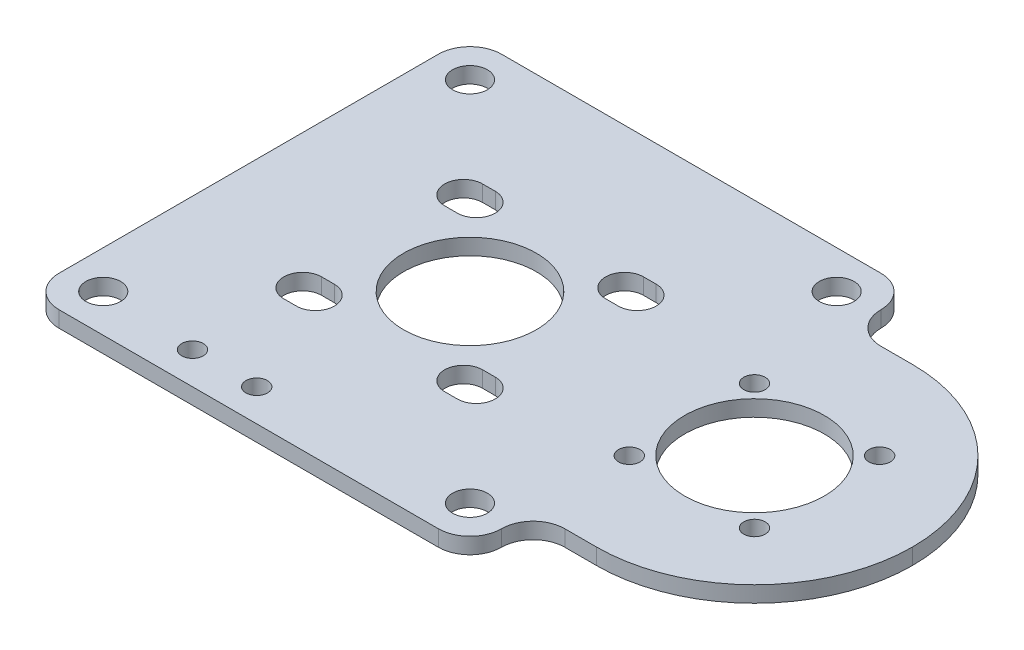
SolidWorks part; units mm, degrees
material "1060 Alloy"
ref_plane "Front Plane" through (0, 0, 0) normal (0, 0, 1) x (1, 0, 0)
ref_plane "Top Plane" through (0, 0, 0) normal (0, 1, 0) x (1, 0, 0)
ref_plane "Right Plane" through (0, 0, 0) normal (1, 0, 0) x (0, 0, -1)
sketch "Sketch1" plane through (0, 0, 0) normal (0, 1, 0) x (1, 0, 0)
  line L0 (0, 0) -> (0, 70)
  line L9 (0, 35) -> (35, 35) construction
  line L10 (35, 35) -> (22.2721, 47.7279) construction
  line L37 (35, 35) -> (35, 53) construction
  line L38 (0, 70) -> (70, 70)
  line L39 (0, 0) -> (70, 0)
  line L41 (80, 35) -> (80, 49) construction
  line L48 (80, 35) -> (70.1005, 44.8995) construction
  line L49 (70, 70) -> (70, 60)
  line L50 (70, 0) -> (70, 10)
  line L51 (70, 60) -> (105, 60)
  line L52 (70, 10) -> (105, 10)
  line L53 (105, 60) -> (105, 10)
  line L54 (21.2721, 47.7279) -> (23.2721, 47.7279) construction
  line L55 (21.2721, 50.7279) -> (23.2721, 50.7279)
  line L56 (21.2721, 44.7279) -> (23.2721, 44.7279)
  line L57 (48.7279, 47.7279) -> (46.7279, 47.7279) construction
  line L58 (48.7279, 50.7279) -> (46.7279, 50.7279)
  line L59 (48.7279, 44.7279) -> (46.7279, 44.7279)
  line L60 (21.2721, 22.2721) -> (23.2721, 22.2721) construction
  line L61 (21.2721, 19.2721) -> (23.2721, 19.2721)
  line L62 (21.2721, 25.2721) -> (23.2721, 25.2721)
  line L63 (48.7279, 22.2721) -> (46.7279, 22.2721) construction
  line L64 (48.7279, 19.2721) -> (46.7279, 19.2721)
  line L65 (48.7279, 25.2721) -> (46.7279, 25.2721)
  line L66 (31.19, 5.08) -> (21.03, 5.08) construction
  line L67 (17.22, 0) -> (35, 0) construction
  line L68 (17.22, 0) -> (17.22, 12.7) construction
  line L69 (17.22, 12.7) -> (35, 12.7) construction
  line L70 (35, 0) -> (35, 12.7) construction
  line L71 (26.11, 12.7) -> (26.11, 0) construction
  circle A19 centre (35, 35) radius 10.5
  circle A20 centre (35, 35) radius 18 construction
  circle A25 centre (80, 35) radius 11.05
  circle A26 centre (80, 35) radius 14 construction
  circle A27 centre (70.1005, 44.8995) radius 1.7
  circle A28 centre (89.8995, 44.8995) radius 1.7
  circle A29 centre (89.8995, 25.1005) radius 1.7
  circle A30 centre (70.1005, 25.1005) radius 1.7
  arc A31 (21.2721, 50.7279) -> (21.2721, 44.7279) centre (21.2721, 47.7279) ccw
  arc A32 (23.2721, 44.7279) -> (23.2721, 50.7279) centre (23.2721, 47.7279) ccw
  arc A33 (48.7279, 50.7279) -> (48.7279, 44.7279) centre (48.7279, 47.7279) cw
  arc A34 (46.7279, 44.7279) -> (46.7279, 50.7279) centre (46.7279, 47.7279) cw
  arc A35 (21.2721, 19.2721) -> (21.2721, 25.2721) centre (21.2721, 22.2721) cw
  arc A36 (23.2721, 25.2721) -> (23.2721, 19.2721) centre (23.2721, 22.2721) cw
  arc A37 (48.7279, 19.2721) -> (48.7279, 25.2721) centre (48.7279, 22.2721) ccw
  arc A38 (46.7279, 25.2721) -> (46.7279, 19.2721) centre (46.7279, 22.2721) ccw
  circle A39 centre (21.03, 5.08) radius 1.7
  circle A40 centre (31.19, 5.08) radius 1.7
  point P6 (18.2721, 47.7279)
  point P14 (26.2721, 47.7279)
  point P21 (47.7279, 47.7279)
  point P23 (35, 35)
  point P39 (80, 35)
  point P42 (22.2721, 47.7279)
  point P52 (22.2721, 22.2721)
  point P60 (47.7279, 22.2721)
  dimension "D4" = 36
  dimension "D9" = 28
  dimension "D7" = 70
  dimension "D1" = 70
  dimension "D2" = 35
  dimension "D8" = 22.1
  dimension "D11" = 45
  dimension "D13" = 50
  dimension "D14" = 25
  dimension "D15" = 8
  dimension "D16" = 12.7
  dimension "D3" = 21
  dimension "D6" = 6
  dimension "D12" = 3.4
  dimension "D18" = 3.4
  dimension "D5" = 45
  dimension "D10" = 45
  dimension "D17" = 17.78
  dimension "D19" = 10.16
  dimension "D20" = 5.08
extrude "Boss-Extrude1" add sketch "Sketch1" along normal blind 2.54
fillet "Fillet1" radius 25 2 edges at (105, 1.27, -10) (105, 1.27, -60)
fillet "Fillet2" radius 5 6 edges at (70, 1.27, -60) (70, 1.27, -10) (0, 1.27, -70) (0, 1.27, 0) (70, 1.27, 0) (70, 1.27, -70)
sketch "Sketch2" plane through (0, 2.54, 0) normal (0, 1, 0) x (1, 0, 0)
  line L0 (0, 65) -> (0, 5) construction
  line L1 (6, 64) -> (64, 64) construction
  line L2 (6, 64) -> (6, 6) construction
  line L3 (6, 6) -> (64, 6) construction
  line L4 (64, 64) -> (64, 6) construction
  line L5 (65, 70) -> (5, 70) construction
  line L6 (5, 0) -> (65, 0) construction
  circle A0 centre (6, 64) radius 2.75
  circle A2 centre (64, 64) radius 2.75
  circle A3 centre (64, 6) radius 2.75
  circle A4 centre (6, 6) radius 2.75
  dimension "D1" = 5.5
  dimension "D2" = 6
  dimension "D3" = 6
  dimension "D4" = 6
extrude "Cut-Extrude1" cut sketch "Sketch2" against normal blind 10
